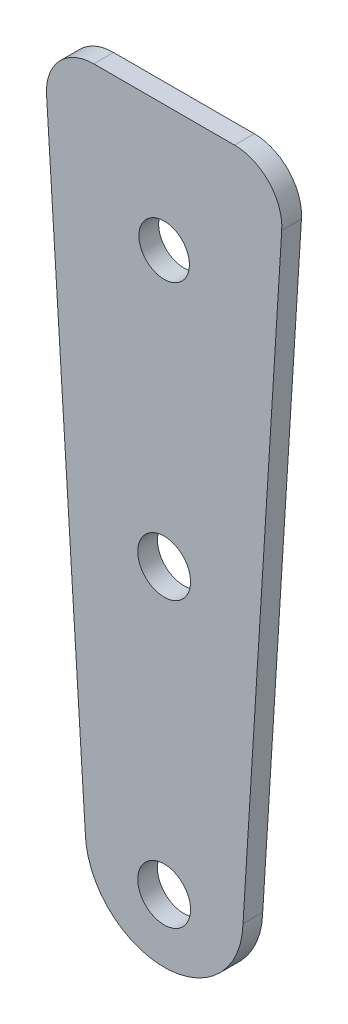
SolidWorks part; units mm, degrees
material "Balsa"
ref_plane "Front Plane" through (0, 0, 0) normal (0, 0, 1) x (1, 0, 0)
ref_plane "Top Plane" through (0, 0, 0) normal (0, 1, 0) x (1, 0, 0)
ref_plane "Right Plane" through (0, 0, 0) normal (1, 0, 0) x (0, 0, -1)
sketch "Sketch1" plane through (0, 0, 0) normal (0, 0, 1) x (1, 0, 0)
  line L0 (0.0147, -3.6458) -> (0.0147, -105.2458) construction
  line L1 (-6.3353, -105.2458) -> (-12.6853, -3.6458)
  line L2 (0.0147, -3.6458) -> (-12.6853, -3.6458) construction
  line L3 (-6.3353, -105.2458) -> (0.0147, -105.2458) construction
  line L4 (0.0147, -3.6458) -> (12.7147, -3.6458) construction
  line L5 (0.0147, -105.2458) -> (6.3647, -105.2458) construction
  line L6 (6.3647, -105.2458) -> (12.7147, -3.6458)
  arc A0 (-6.3353, -105.2458) -> (6.3647, -105.2458) centre (0.0147, -105.1143) ccw
  arc A1 (-12.6853, -3.6458) -> (12.7147, -3.6458) centre (0.0147, -3.835) cw
  dimension "D3" = 12.7
  dimension "D1" = 101.6
  dimension "D2" = 25.4
extrude "Boss-Extrude1" add sketch "Sketch1" along normal blind 76.2 and the other way blind 76.2
sketch "Sketch4" plane through (0, 0, 0) normal (1, 0, 0) x (0, 0, -1)
  line L1 (-47.498, -73.5246) -> (-47.498, -51.2996)
  line L3 (-76.2, -111.4656) -> (76.2, -111.4656) construction
  line L4 (-47.498, -51.2996) -> (47.625, -51.2996)
  line L9 (47.625, -73.5246) -> (47.625, -51.2996)
  line L10 (76.2, -73.5246) -> (47.625, -73.5246)
  line L11 (-76.2, 8.8664) -> (-76.2, -28.6823)
  line L12 (-76.2, 8.8664) -> (76.2, 8.8664)
  line L13 (76.2, 8.8664) -> (76.2, -73.5246)
  line L15 (-47.498, -73.5246) -> (-60.198, -73.5246)
  line L16 (-60.198, -73.5246) -> (-60.198, -111.4656)
  line L17 (-76.2, -111.4656) -> (76.2, -111.4656) construction
  line L18 (-76.2, -28.6823) -> (-76.2, -111.4656)
  line L19 (-76.2, -111.4656) -> (-60.198, -111.4656)
  dimension "D2" = 28.575
  dimension "D1" = 22.225
  dimension "D5" = 12.7
  dimension "D6" = 120.332
  dimension "D4" = 60.166
  dimension "D3" = 28.702
extrude "Cut-Extrude1" cut sketch "Sketch4" against normal through all both and the other way through all
fillet "Fillet1" radius 3.81 6 edges at (8.3473, -73.5246, 53.848) (9.7364, -51.2996, -0.0635) (-8.3178, -73.5246, 53.848) (-9.7069, -51.2996, -0.0635) (8.3473, -73.5246, -61.9125) (-8.3178, -73.5246, -61.9125)
sketch "Sketch6" plane through (0, 0, -76.2) normal (0, 0, -1) x (-1, 0, 0)
  line L0 (8.1441, -76.3269) -> (4.9629, -76.3269)
  line L1 (-4.9629, -76.3269) -> (-8.1441, -76.3269)
  arc A2 (4.9629, -76.3269) -> (-4.9629, -76.3269) centre (0, -76.3269) ccw
  arc A3 (8.1441, -76.3269) -> (-8.1441, -76.3269) centre (0, -76.3269) ccw
extrude "Boss-Extrude2" [suppressed] add sketch "Sketch6" against normal up to surface (28.575 mm away)
sketch "Sketch7" [suppressed] plane through (0, 0, -47.625) normal (0, 0, -1) x (-1, 0, 0)
  line L0 (-9.5331, -54.1019) -> (-6.3519, -54.1019)
  line L1 (6.3519, -54.1019) -> (9.5331, -54.1019)
  arc A0 (-6.3519, -54.1019) -> (6.3519, -54.1019) centre (0, -56.9157) cw
  arc A1 (-9.5331, -54.1019) -> (9.5331, -54.1019) centre (0, -57.5231) cw
sketch "Sketch14" plane through (0, 0, -47.625) normal (0, 0, -1) x (-1, 0, 0)
  line L0 (-0.0147, -51.2996) -> (-0.0147, -95.2556) construction
  line L1 (5.6513, -51.2996) -> (-5.6808, -51.2996) construction
  circle A0 centre (-0.0147, -61.4596) radius 2.032
  dimension "D2" = 4.064
  dimension "D1" = 10.16
extrude "Cut-Extrude8" cut sketch "Sketch14" against normal through all
sketch "Sketch15" plane through (0, 0, 0) normal (0, 1, 0) x (1, 0, 0)
  line L1 (-65.0326, 101.5228) -> (31.6992, 101.5228)
  line L2 (-65.0326, 101.5228) -> (-65.0326, -45.9105)
  line L3 (-65.0326, -45.9105) -> (31.6992, -45.9105)
  line L4 (31.6992, 101.5228) -> (31.6992, -45.9105)
  line L9 (-5.6513, -47.498) -> (5.6808, -47.498) construction
  line L10 (-65.0326, -47.498) -> (61.2262, -47.498)
  line L11 (-65.0326, -47.498) -> (-65.0326, -78.792)
  line L12 (-65.0326, -78.792) -> (61.2262, -78.792)
  line L13 (61.2262, -47.498) -> (61.2262, -78.792)
  line L14 (4.2918, -47.498) -> (8.1018, -47.498) construction
  dimension "D1" = 1.5875
extrude "Cut-Extrude9" cut sketch "Sketch15" against normal through all both and the other way through all
sketch "Sketch16" plane through (0, 0, 47.498) normal (0, 0, 1) x (1, 0, 0)
  line L0 (0.0147, -51.2996) -> (0.0147, -111.4656) construction
  line L1 (-5.6513, -51.2996) -> (5.6808, -51.2996) construction
  arc A0 (-6.3353, -105.2458) -> (6.3647, -105.2458) centre (0.0147, -105.1143) ccw construction
  circle A1 centre (0.0147, -106.3856) radius 2.127
  circle A2 centre (0.0147, -83.5256) radius 2.127
  dimension "D3" = 4.254
  dimension "D1" = 5.08
  dimension "D2" = 27.94
extrude "Cut-Extrude10" cut sketch "Sketch16" against normal through all both
equation "\"D4@Sketch4\"=0.5*\"D6@Sketch4\""
